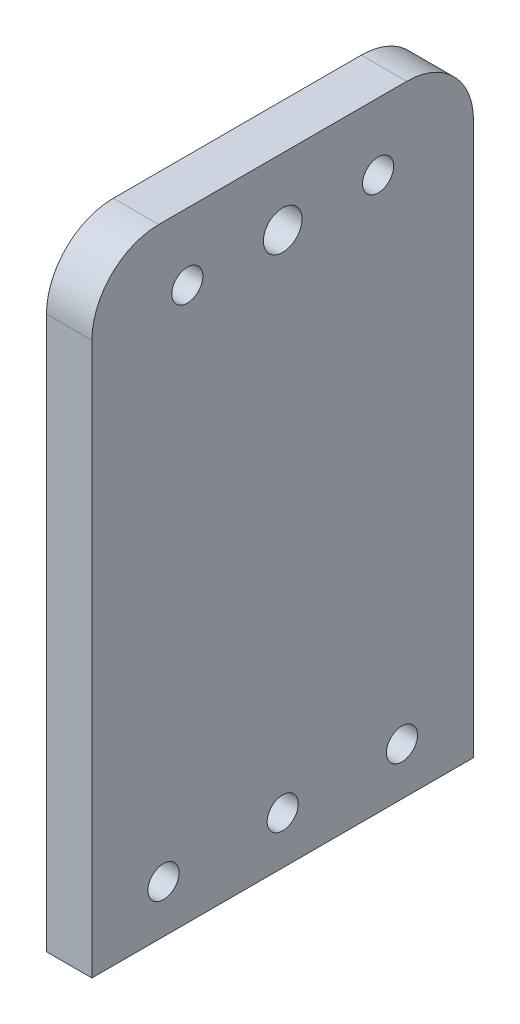
SolidWorks part; units mm, degrees
ref_plane "Front Plane" through (0, 0, 0) normal (0, 0, 1) x (1, 0, 0)
ref_plane "Top Plane" through (0, 0, 0) normal (0, 1, 0) x (1, 0, 0)
ref_plane "Right Plane" through (0, 0, 0) normal (1, 0, 0) x (0, 0, -1)
sketch "Sketch1" plane through (0, 0, 0) normal (1, 0, 0) x (0, 0, -1)
  line L1 (0, 0) -> (40, 0)
  line L2 (0, 0) -> (0, 57.9)
  line L3 (7, 64.9) -> (33, 64.9)
  line L4 (40, 0) -> (40, 57.9)
  arc A1 (33, 64.9) -> (40, 57.9) centre (33, 57.9) cw
  arc A2 (0, 57.9) -> (7, 64.9) centre (7, 57.9) cw
  point P7 (40, 64.9)
  point P10 (0, 64.9)
  dimension "D3" = 7
  dimension "D1" = 40
  dimension "D2" = 57.9
extrude "Boss-Extrude1" add sketch "Sketch1" along normal blind 4.7625 contours L2 L1 L4 region at (0, 32.1977, -20)
ref_axis "Axis1" through (4.7625, 64.9, -20) along (0, -1, 0)
ref_plane "Plane1" through (0, 0, -20) normal (0, 0, -1) x (-1, 0, 0)
hole_wizard "#4 Clearance Hole4" positions "Sketch6" profile "Sketch7" hole size "#4" standard "ANSI Inch" end condition through all
sketch "Sketch6" plane through (4.7625, 0, 0) normal (1, 0, 0) x (0, 0, -1)
  line L0 (0, 0) -> (40, 0) construction
  line L1 (20, -49.3392) -> (20, 49.3392) construction
  point P0 (7.5, 5)
  point P2 (20, 5)
  point P8 (20, 0)
  point P11 (32.5, 5)
  dimension "D1" = 12.5
  dimension "D2" = 5
sketch "Sketch7" plane through (4.7625, 5, -7.5) normal (0, 1, 0) x (0, 0, -1)
  line L0 (0, 0) -> (0, 4.7625)
  line L1 (0, 4.7625) -> (1.6319, 4.7625)
  line L2 (1.6319, 4.7625) -> (1.6319, 0)
  line L5 (1.6319, 0) -> (0, 0)
  line L11 (0, -6.35) -> (0, 107.95) construction
  dimension "Thru Hole Dia." = 3.2639
  dimension "Thru Hole Depth" = 4.7625
sketch "Sketch10" plane through (4.7625, 0, 0) normal (1, 0, 0) x (0, 0, -1)
  line L0 (0, 0) -> (40, 0) construction
  line L1 (20, 64.9) -> (20, -2.7097) construction
  circle A0 centre (20, 57.9) radius 2.025
  dimension "D2" = 4.05
  dimension "D1" = 57.9
extrude "Cut-Extrude1" cut sketch "Sketch10" against normal blind 10
hole_wizard "#4 Clearance Hole3" positions "Sketch11" profile "Sketch12" hole size "#4" standard "ANSI Inch" end condition through all
sketch "Sketch11" plane through (4.7625, 0, 0) normal (1, 0, 0) x (0, 0, -1)
  line L0 (20, -49.3392) -> (20, 49.3392) construction
  circle A1 centre (20, 57.9) radius 2.025 construction
  point P0 (10, 57.9)
  point P16 (30, 57.9)
  dimension "D1" = 10
sketch "Sketch12" plane through (4.7625, 57.9, -10) normal (0, 1, 0) x (0, 0, -1)
  line L0 (0, 0) -> (0, 4.7625)
  line L1 (0, 4.7625) -> (1.6319, 4.7625)
  line L2 (1.6319, 4.7625) -> (1.6319, 0)
  line L5 (1.6319, 0) -> (0, 0)
  line L11 (0, -6.35) -> (0, 107.95) construction
  dimension "Thru Hole Dia." = 3.2639
  dimension "Thru Hole Depth" = 4.7625
equation "\"Shaft Height\"= 32.5 + 25.4"
equation "\"D2@Sketch1\"=\"Shaft Height\""
equation "\"D1@Sketch10\"=\"Shaft Height\""
equation "\"D1@Boss-Extrude1\"=(3/16)*25.4"
